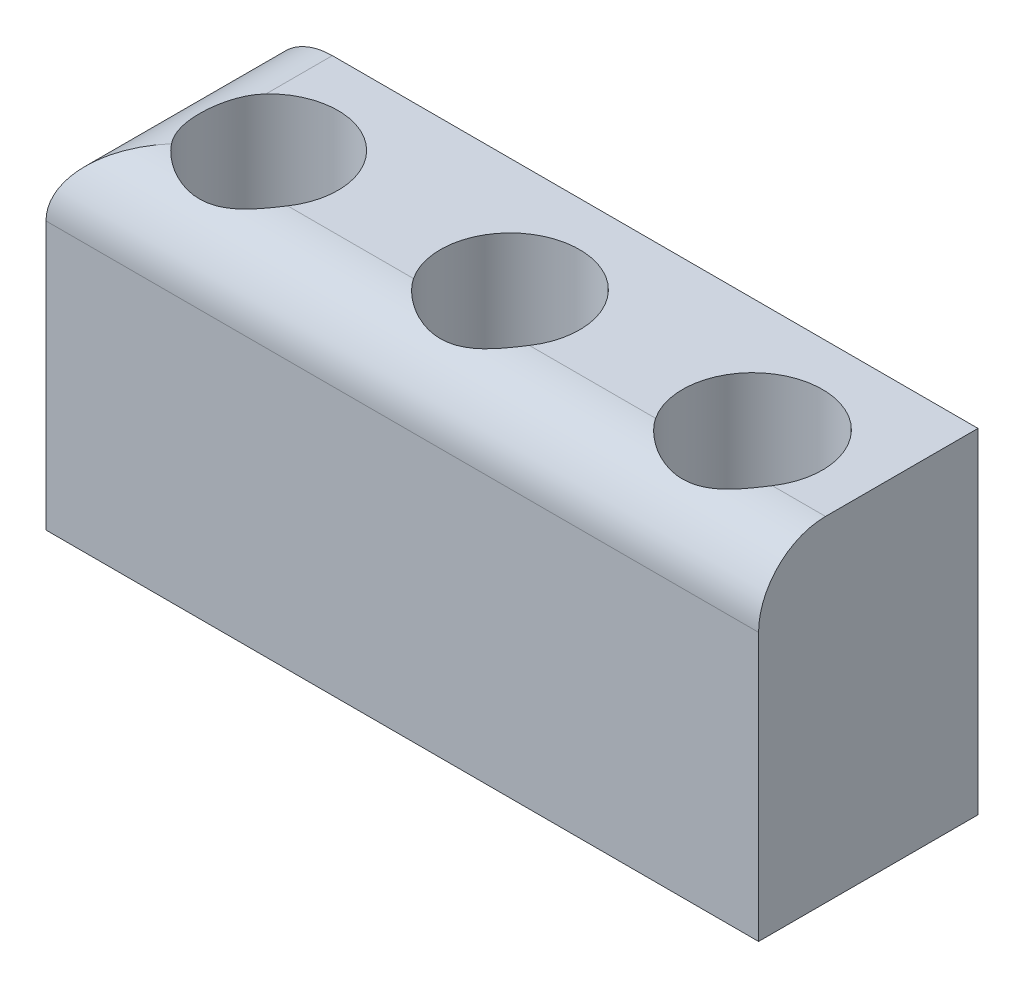
SolidWorks part; units mm, degrees
ref_plane "Front Plane" through (0, 0, 0) normal (0, 0, 1) x (1, 0, 0)
ref_plane "Top Plane" through (0, 0, 0) normal (0, 1, 0) x (1, 0, 0)
ref_plane "Right Plane" through (0, 0, 0) normal (1, 0, 0) x (0, 0, -1)
sketch "Sketch1" plane through (0, 0, 0) normal (0, 1, 0) x (1, 0, 0)
  line L1 (0, 0) -> (21.2932, 0)
  line L2 (0, 0) -> (0, 6.5562)
  line L3 (0, 6.5562) -> (21.2932, 6.5562)
  line L4 (21.2932, 0) -> (21.2932, 6.5562)
  circle A0 centre (10.7125, 3.1522) radius 2.08
  circle A1 centre (3.5025, 3.1522) radius 2.07
  circle A2 centre (17.9595, 3.1522) radius 2.09
  dimension "D1" = 4.16
  dimension "D2" = 4.14
  dimension "D3" = 4.18
extrude "Boss-Extrude1" add sketch "Sketch1" along normal blind 10 contours L1 L4 L3 L2 A2 A1 A0 region at (0.2228, 0, -3.2781)
fillet "Fillet1" radius 2 2 edges at (10.6466, 10, 0) (0, 10, -3.2781)
